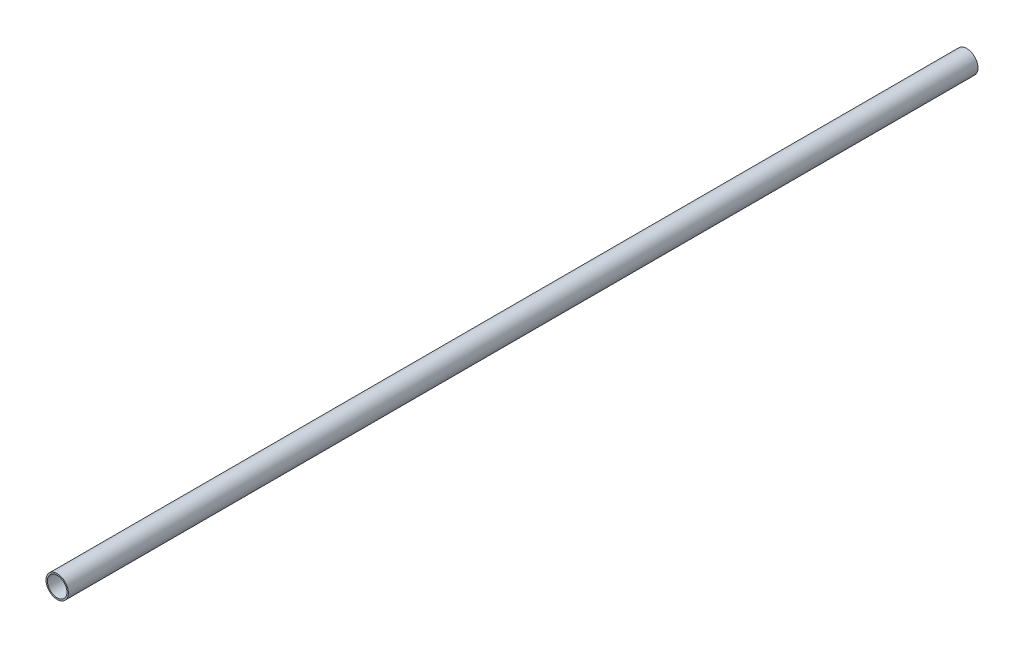
SolidWorks part; units mm, degrees
material "Poltrusion Carbon Fiber"
ref_plane "Front Plane" through (0, 0, 0) normal (0, 0, 1) x (1, 0, 0)
ref_plane "Top Plane" through (0, 0, 0) normal (0, 1, 0) x (1, 0, 0)
ref_plane "Right Plane" through (0, 0, 0) normal (1, 0, 0) x (0, 0, -1)
sketch "Эскиз1" plane through (0, 0, 0) normal (0, 0, 1) x (1, 0, 0)
  circle A0 centre (0, 0) radius 8
  circle A1 centre (0, 0) radius 7
  dimension "D1" = 16
  dimension "D2" = 1
extrude "Бобышка-Вытянуть1" add sketch "Эскиз1" along normal mid plane 650
ref_axis "Ось1" through (0, 0, 325) along (0, 0, -1)
